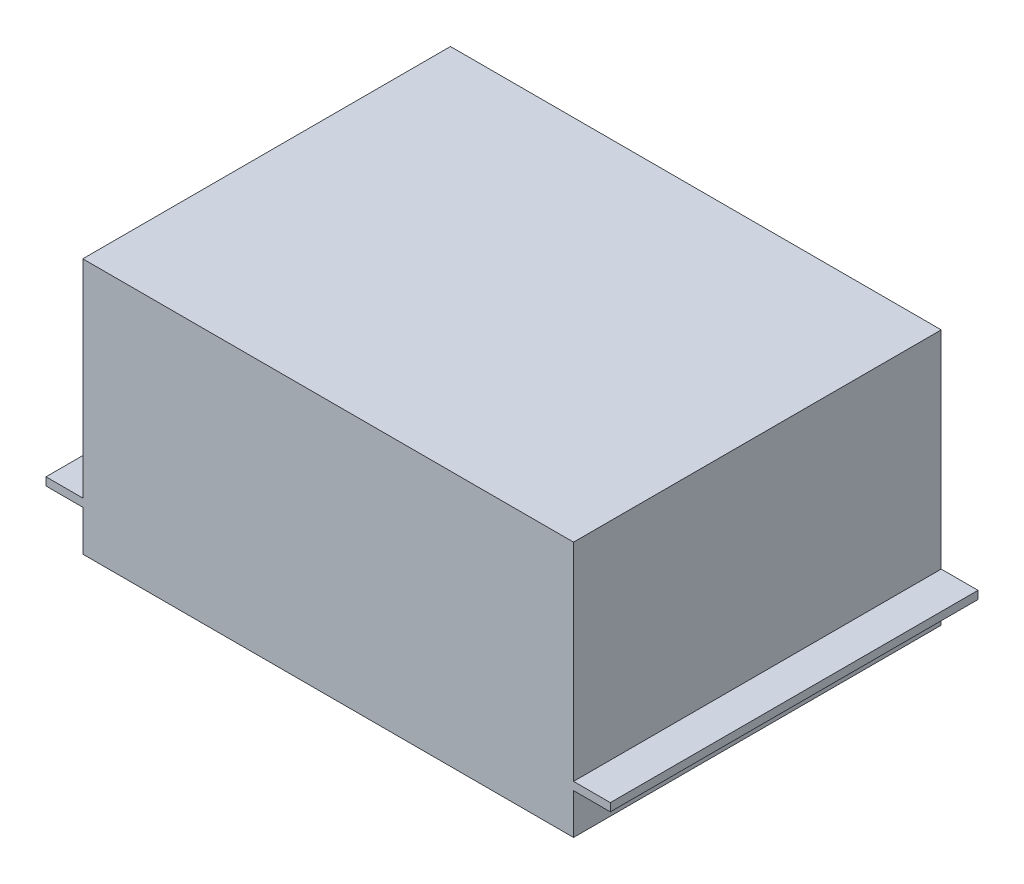
SolidWorks part; units mm, degrees
ref_plane "Front Plane" through (0, 0, 0) normal (0, 0, 1) x (1, 0, 0)
ref_plane "Top Plane" through (0, 0, 0) normal (0, 1, 0) x (1, 0, 0)
ref_plane "Right Plane" through (0, 0, 0) normal (1, 0, 0) x (0, 0, -1)
sketch "Sketch1" plane through (0, 0, 0) normal (0, 1, 0) x (1, 0, 0)
  line L1 (-153.5, -115) -> (153.5, -115)
  line L2 (-153.5, -115) -> (-153.5, 115)
  line L3 (-153.5, 115) -> (153.5, 115)
  line L4 (153.5, -115) -> (153.5, 115)
  line L5 (-153.5, -115) -> (153.5, 115) construction
  line L6 (-153.5, 115) -> (153.5, -115) construction
  line L7 (-176.5, -115) -> (176.5, -115)
  line L8 (-176.5, -115) -> (-176.5, 115)
  line L9 (-176.5, 115) -> (176.5, 115)
  line L10 (176.5, -115) -> (176.5, 115)
  line L11 (-176.5, -115) -> (176.5, 115) construction
  line L12 (-176.5, 115) -> (176.5, -115) construction
  point P0 (0, 0)
  point P6 (0, 0)
  dimension "D1" = 307
  dimension "D2" = 230
  dimension "D3" = 353
extrude "Boss-Extrude1" add sketch "Sketch1" along normal blind 160 contours L1 L4 L3 L2 region at (0, 0, 0)
extrude "Boss-Extrude2" add sketch "Sketch1<3>" along normal blind 5 from offset 25.4 contours L9 L8 L7 L2 | L7 L10 L9 L4 region at (-165, 0, 0) region at (165, 0, 0)
sketch "Sketch1<3>" plane through (0, 0, 0) normal (0, 1, 0) x (1, 0, 0) same geometry as "Sketch1"
sketch "Sketch2" plane through (0, 30.4, 0) normal (0, 1, 0) x (1, 0, 0)
  line L0 (176.5, -115) -> (176.5, 115) construction
  line L1 (161, -4) -> (169, -4)
  line L3 (161, 4) -> (169, 4)
  line L8 (165, 4) -> (165, -4) construction
  ellipse E0 centre (161, 0) end of major axis (161, 4) minor radius 3.5 (161, -4) -> (161, 4) cw
  ellipse E1 centre (169, 0) end of major axis (169, 4) minor radius 3.5 (169, -4) -> (169, 4) ccw
  point P8 (176.5, 0)
  dimension "D2" = 11.5
  dimension "D1" = 8
  dimension "D3" = 15
  dimension "D4" = 4
